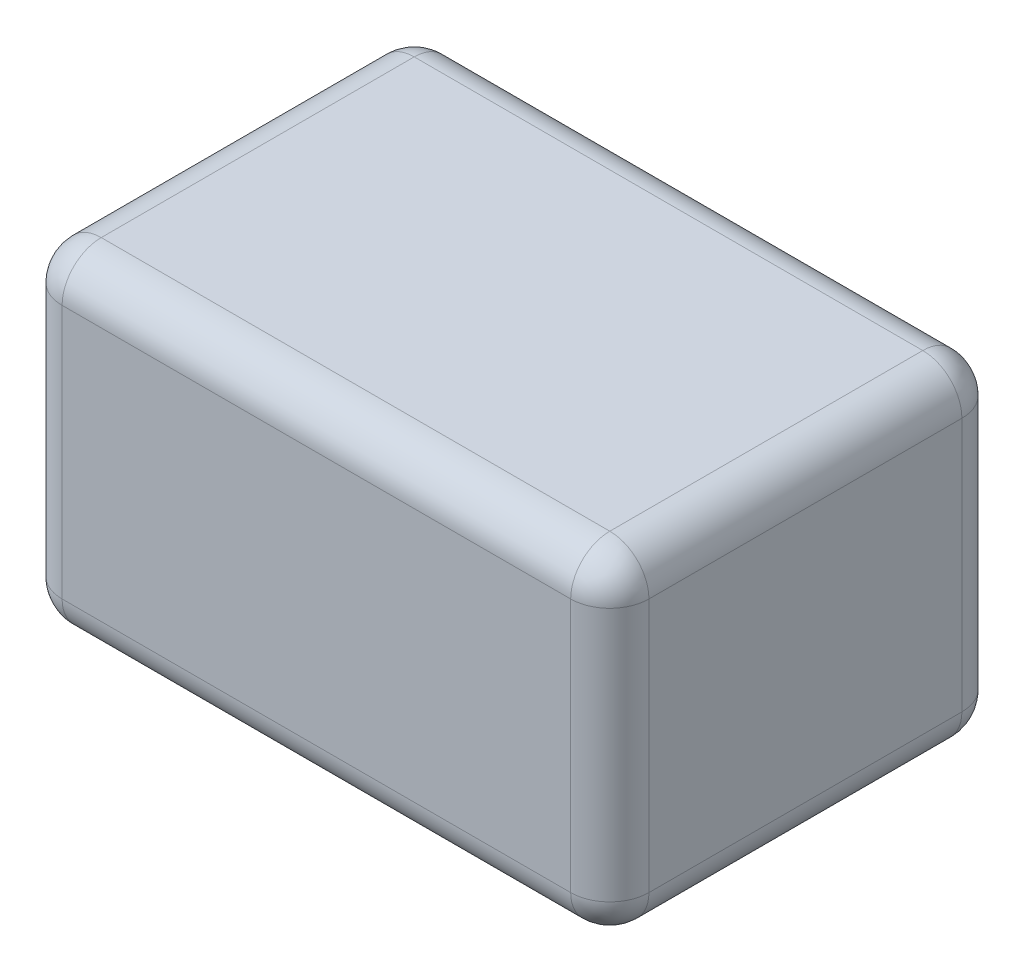
SolidWorks part; units mm, degrees
ref_plane "Front Plane" through (0, 0, 0) normal (0, 0, 1) x (1, 0, 0)
ref_plane "Top Plane" through (0, 0, 0) normal (0, 1, 0) x (1, 0, 0)
ref_plane "Right Plane" through (0, 0, 0) normal (1, 0, 0) x (0, 0, -1)
sketch "Sketch1" plane through (0, 0, 0) normal (0, 1, 0) x (1, 0, 0)
  line L1 (-30, -20) -> (30, -20)
  line L2 (-30, -20) -> (-30, 20)
  line L3 (-30, 20) -> (30, 20)
  line L4 (30, -20) -> (30, 20)
  line L5 (-30, -20) -> (30, 20) construction
  line L6 (-30, 20) -> (30, -20) construction
  point P0 (0, 0)
  dimension "D1" = 60
  dimension "D2" = 40
extrude "Boss-Extrude1" add sketch "Sketch1" along normal blind 34
fillet "Fillet1" radius 4 12 edges at (30, 17, 20) (0, 34, 20) (30, 34, 0) (-30, 34, 0) (-30, 17, 20) (-30, 0, 0) (0, 0, 20) (30, 0, 0) (30, 17, -20) (0, 34, -20) (-30, 17, -20) (0, 0, -20)
